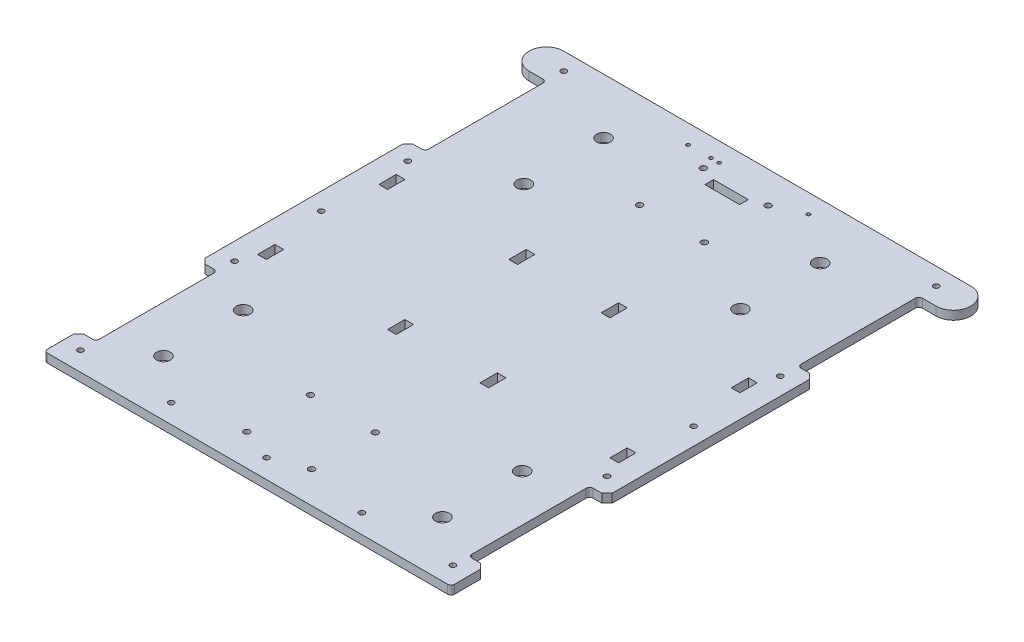
SolidWorks part; units mm, degrees
material "Teak"
ref_plane "Front Plane" through (0, 0, 0) normal (0, 0, 1) x (1, 0, 0)
ref_plane "Top Plane" through (0, 0, 0) normal (0, 1, 0) x (1, 0, 0)
ref_plane "Right Plane" through (0, 0, 0) normal (1, 0, 0) x (0, 0, -1)
sketch "Sketch1" plane through (0, 0, 0) normal (0, 1, 0) x (1, 0, 0)
  line L0 (0, 170) -> (0, -130) construction
  line L1 (-117.5, 0) -> (117.5, 0) construction
  line L2 (-117.5, -130) -> (117.5, -130)
  line L3 (117.5, -130) -> (117.5, -110)
  line L4 (117.5, -110) -> (107.5, -110)
  line L5 (107.5, -110) -> (107.5, -40)
  line L6 (107.5, -40) -> (117.5, -40)
  line L7 (117.5, -40) -> (117.5, 80)
  line L8 (117.5, 80) -> (107.5, 80)
  line L9 (107.5, 80) -> (107.5, 150)
  line L10 (107.5, 150) -> (127.5, 150)
  line L11 (-107.5, 150) -> (-127.5, 150)
  line L12 (-107.5, 80) -> (-107.5, 150)
  line L13 (-117.5, 80) -> (-107.5, 80)
  line L14 (-117.5, -40) -> (-117.5, 80)
  line L15 (-107.5, -40) -> (-117.5, -40)
  line L16 (-107.5, -110) -> (-107.5, -40)
  line L17 (-117.5, -110) -> (-107.5, -110)
  line L18 (-117.5, -130) -> (-117.5, -110)
  line L19 (127.5, 150) -> (127.5, 170)
  line L20 (127.5, 170) -> (-127.5, 170)
  line L21 (-127.5, 150) -> (-127.5, 170)
  point P5 (0, 0)
  dimension "D1" = 300
  dimension "D2" = 20
  dimension "D3" = 20
  dimension "D5" = 10
  dimension "D6" = 70
  dimension "D7" = 70
  dimension "D8" = 255
  dimension "D9" = 20
extrude "Boss-Extrude1" add sketch "Sketch1" along normal blind 5
fillet "Fillet3" 2 edges at (127.5, 2.5, -150) (127.5, 2.5, -170) type full round first side face at (117.5, 2.5, -150) second side face at (0, 2.5, -170) middle face at (127.5, 2.5, -160)
fillet "Fillet4" 2 edges at (-127.5, 2.5, -170) (-127.5, 2.5, -150) type full round first side face at (-5, 2.5, -170) second side face at (-117.5, 2.5, -150) middle face at (-127.5, 2.5, -160)
fillet "Fillet2" radius 2 10 edges at (107.5, 2.5, 40) (107.5, 2.5, -150) (107.5, 2.5, -80) (107.5, 2.5, 110) (-107.5, 2.5, -80) (-107.5, 2.5, 110) (-107.5, 2.5, 40) (-107.5, 2.5, -150) (-117.5, 2.5, 130) (117.5, 2.5, 130)
sketch "Sketch2" plane through (0, 5, 0) normal (0, 1, 0) x (1, 0, 0)
  line L0 (0, -130) -> (0, 90) construction
  line L1 (-115.5, -130) -> (115.5, -130) construction
  line L2 (107.5, 82) -> (107.5, 148) construction
  line L4 (117.5, -40) -> (117.5, 80) construction
  line L5 (117.5, -128) -> (117.5, -110) construction
  arc A0 (117.5, 150) -> (117.5, 170) centre (117.5, 160) ccw construction
  circle A1 centre (107.5, 160) radius 1.6
  circle A2 centre (107.5, 20) radius 1.6
  circle A3 centre (107.5, -119) radius 1.6
  circle A4 centre (0, -119) radius 1.6
  circle A5 centre (-107.5, -119) radius 1.6
  circle A6 centre (-107.5, 20) radius 1.6
  circle A7 centre (-107.5, 160) radius 1.6
  circle A8 centre (55, -119) radius 1.6
  circle A9 centre (-55, -119) radius 1.6
  circle A10 centre (-107.5, 70) radius 1.6
  circle A11 centre (107.5, 70) radius 1.6
  circle A12 centre (-107.5, -30) radius 1.6
  circle A13 centre (107.5, -30) radius 1.6
  point P17 (127.5, 160)
  point P26 (117.5, 20)
  point P30 (117.5, -119)
  dimension "D1" = 3.2
  dimension "D2" = 2
  dimension "D3" = 10
  dimension "D4" = 2
  dimension "D5" = 2
  dimension "D6" = 2
  dimension "D7" = 2
extrude "layer fix hole" cut sketch "Sketch2" against normal through all
chamfer "Chamfer1" distance 3 angle 45 6 edges at (117.5, 2.5, 110) (-117.5, 2.5, -80) (-117.5, 2.5, 40) (-117.5, 2.5, 110) (117.5, 2.5, -80) (117.5, 2.5, 40)
sketch "Sketch9" plane through (0, 0, 0) normal (0, -1, 0) x (1, 0, 0)
  line L0 (107.5, -115) -> (-119.4618, -115) construction
  line L1 (107.5, -82) -> (107.5, -148) construction
  line L2 (107.5, 75) -> (-117.246, 75) construction
  line L3 (107.5, 108) -> (107.5, 42) construction
  line L4 (-117.5, -20) -> (128.0189, -20) construction
  line L5 (0, 75) -> (0, -115) construction
  line L6 (-62.5, -96.3983) -> (-62.5, -133.6017) construction
  line L7 (-107.5, -148) -> (-107.5, -82) construction
  line L8 (-117.5, -77) -> (-117.5, 37) construction
  line L9 (-80.5, 98) -> (-80.5, 52) construction
  line L10 (-80.5, 52) -> (80.5, 52) construction
  line L11 (80.5, 52) -> (80.5, 98) construction
  line L12 (80.5, 98) -> (-80.5, 98) construction
  line L14 (-107.5, 42) -> (-107.5, 108) construction
  circle A0 centre (-62.5, -138) radius 4
  circle A1 centre (-62.5, -92) radius 4
  circle A2 centre (62.5, -92) radius 4
  circle A3 centre (62.5, -138) radius 4
  circle A4 centre (80.5, 98) radius 4
  circle A5 centre (80.5, 52) radius 4
  circle A6 centre (-80.5, 98) radius 4
  circle A7 centre (-80.5, 52) radius 4
  point P16 (-62.5, -115)
  dimension "D2" = 8
  dimension "D1" = 45
  dimension "D3" = 23
  dimension "D4" = 27
extrude "Motor fix hole" cut sketch "Sketch9" against normal up to next
sketch "Sketch10" plane through (0, 0, 0) normal (0, -1, 0) x (1, 0, 0)
  line L0 (-117.5, -20) -> (130.9103, -20) construction
  line L1 (-117.5, -77) -> (-117.5, 37) construction
  line L2 (0, 130) -> (0, -170) construction
  line L3 (-115.5, 130) -> (115.5, 130) construction
  line L4 (117.5, -170) -> (-117.5, -170) construction
  line L5 (-18.6898, 75) -> (18.6898, 75) construction
  line L6 (-23.6898, 116.7418) -> (23.6898, 116.7418) construction
  line L7 (-23.6898, 116.7418) -> (-23.6898, 70) construction
  line L8 (-23.6898, 70) -> (23.6898, 70) construction
  line L9 (23.6898, 116.7418) -> (23.6898, 70) construction
  line L10 (-23.6898, 116.7418) -> (23.6898, 70) construction
  line L11 (-23.6898, 70) -> (23.6898, 116.7418) construction
  line L12 (18.6898, 111.7418) -> (18.6898, 75) construction
  line L13 (-18.6898, 111.7418) -> (18.6898, 111.7418) construction
  line L14 (-18.6898, 111.7418) -> (-18.6898, 75) construction
  line L18 (-18.6898, -151.7418) -> (-18.6898, -115) construction
  line L19 (-18.6898, -151.7418) -> (18.6898, -151.7418) construction
  line L25 (18.6898, -151.7418) -> (18.6898, -115) construction
  line L28 (-23.6898, -110) -> (23.6898, -156.7418) construction
  line L30 (-23.6898, -156.7418) -> (23.6898, -110) construction
  line L32 (23.6898, -156.7418) -> (23.6898, -110) construction
  line L33 (-23.6898, -110) -> (23.6898, -110) construction
  line L34 (-23.6898, -156.7418) -> (-23.6898, -110) construction
  line L36 (-23.6898, -156.7418) -> (23.6898, -156.7418) construction
  line L37 (-18.6898, -115) -> (18.6898, -115) construction
  circle A0 centre (18.6898, 75) radius 1.75
  circle A1 centre (-18.6898, 75) radius 1.75
  circle A2 centre (-18.6898, 111.7418) radius 1.75
  circle A3 centre (18.6898, 111.7418) radius 1.75
  circle A4 centre (18.6898, -151.7418) radius 1.75
  circle A5 centre (-18.6898, -151.7418) radius 1.75
  circle A6 centre (-18.6898, -115) radius 1.75
  circle A7 centre (18.6898, -115) radius 1.75
  point P10 (0, 93.3709)
  point P37 (0, -133.3709)
  dimension "D3" = 3.5
  dimension "D1" = 37.3795
  dimension "D2" = 5
  dimension "D4" = 36.7418
  dimension "D5" = 90
extrude "Motor driver fix hole" cut sketch "Sketch10" against normal up to next
sketch "Sketch11" plane through (0, 0, 0) normal (0, -1, 0) x (1, 0, 0)
  line L0 (0, -170) -> (0, -144.1108) construction
  line L1 (117.5, -170) -> (-117.5, -170) construction
  line L2 (0, -144.1108) -> (0, -110.0028) construction
  line L5 (-37.465, -159) -> (37.465, -159) construction
  line L7 (34.2319, -158.1371) -> (37.465, -159) construction
  line L8 (-37.465, -159) -> (-34.2319, -158.1371) construction
  line L10 (-10, -144) -> (10, -144)
  line L11 (-10, -144) -> (-10, -149)
  line L12 (-10, -149) -> (10, -149)
  line L13 (10, -144) -> (10, -149)
  line L14 (-10, -144) -> (10, -149) construction
  line L15 (-10, -149) -> (10, -144) construction
  circle A0 centre (-34.7373, -159) radius 1
  circle A1 centre (-21.5138, -159) radius 1
  circle A2 centre (-16.8148, -159) radius 1
  circle A3 centre (34.7373, -159) radius 1
  point P1 (0, -146.5)
  point P5 (0, -149.001)
  dimension "D2" = 2.7277
  dimension "D6" = 2
  dimension "D1" = 2.7277
  dimension "D3" = 13.2235
  dimension "D4" = 4.699
  dimension "D5" = 51.5521
  dimension "D7" = 20
  dimension "D8" = 5
  dimension "D9" = 11
  dimension "D10" = 10
extrude "QTR8a fix hole" cut sketch "Sketch11" against normal blind 10
sketch "Sketch 12" plane through (0, 5, 0) normal (0, 1, 0) x (1, 0, 0)
  line L0 (-39.1667, 170) -> (-39.1667, -135.4982) construction
  line L1 (117.5, 170) -> (-117.5, 170) construction
  line L2 (-117.5, 20) -> (117.5, 20) construction
  line L12 (24.1667, 60) -> (29.1667, 60)
  line L37 (-117.5, -120.5) -> (-39.1667, -120.5) construction
  line L38 (39.1667, 170) -> (39.1667, -135.4982) construction
  line L39 (-39.1667, -120.5) -> (39.1667, -120.5) construction
  line L40 (39.1667, -120.5) -> (117.5, -120.5) construction
  line L41 (117.5, -128) -> (117.5, -113) construction
  line L42 (-117.5, -113) -> (-117.5, -128) construction
  line L43 (99.1667, 60) -> (99.1667, 50)
  line L44 (24.1667, 60) -> (24.1667, 50)
  line L45 (24.1667, 50) -> (29.1667, 50)
  line L46 (29.1667, 60) -> (29.1667, 50)
  line L86 (-117.5, 77) -> (-117.5, -37) construction
  line L87 (117.5, -37) -> (117.5, 77) construction
  line L88 (24.1667, -10) -> (29.1667, -10)
  line L89 (29.1667, -20) -> (29.1667, -10)
  line L90 (24.1667, -20) -> (29.1667, -20)
  line L91 (24.1667, -20) -> (24.1667, -10)
  line L92 (99.1667, 60) -> (104.1667, 60)
  line L93 (104.1667, 60) -> (104.1667, 50)
  line L94 (99.1667, 50) -> (104.1667, 50)
  line L95 (99.1667, -10) -> (104.1667, -10)
  line L96 (104.1667, -20) -> (104.1667, -10)
  line L97 (99.1667, -20) -> (104.1667, -20)
  line L98 (99.1667, -20) -> (99.1667, -10)
  line L99 (-104.1667, 60) -> (-99.1667, 60)
  line L100 (-29.1667, 60) -> (-29.1667, 50)
  line L101 (-104.1667, 60) -> (-104.1667, 50)
  line L102 (-104.1667, 50) -> (-99.1667, 50)
  line L103 (-99.1667, 60) -> (-99.1667, 50)
  line L104 (-104.1667, -10) -> (-99.1667, -10)
  line L105 (-99.1667, -20) -> (-99.1667, -10)
  line L106 (-104.1667, -20) -> (-99.1667, -20)
  line L107 (-104.1667, -20) -> (-104.1667, -10)
  line L108 (-29.1667, 60) -> (-24.1667, 60)
  line L109 (-24.1667, 60) -> (-24.1667, 50)
  line L110 (-29.1667, 50) -> (-24.1667, 50)
  line L111 (-29.1667, -10) -> (-24.1667, -10)
  line L112 (-24.1667, -20) -> (-24.1667, -10)
  line L113 (-29.1667, -20) -> (-24.1667, -20)
  line L114 (-29.1667, -20) -> (-29.1667, -10)
  line L115 (-245.8333, 20) -> (-10.8333, 20) construction
  line L117 (-89.1667, 170) -> (-89.1667, -135.4982) construction
  point P0 (29.1667, 55)
  dimension "D1" = 5
  dimension "D2" = 10
  dimension "D3" = 10
  dimension "D4" = 2
  dimension "D7" = 60
  dimension "D8" = 10
  dimension "D5" = 2
  dimension "D6" = 70
extrude "Battery fixed hole" cut sketch "Sketch 12" against normal through all
